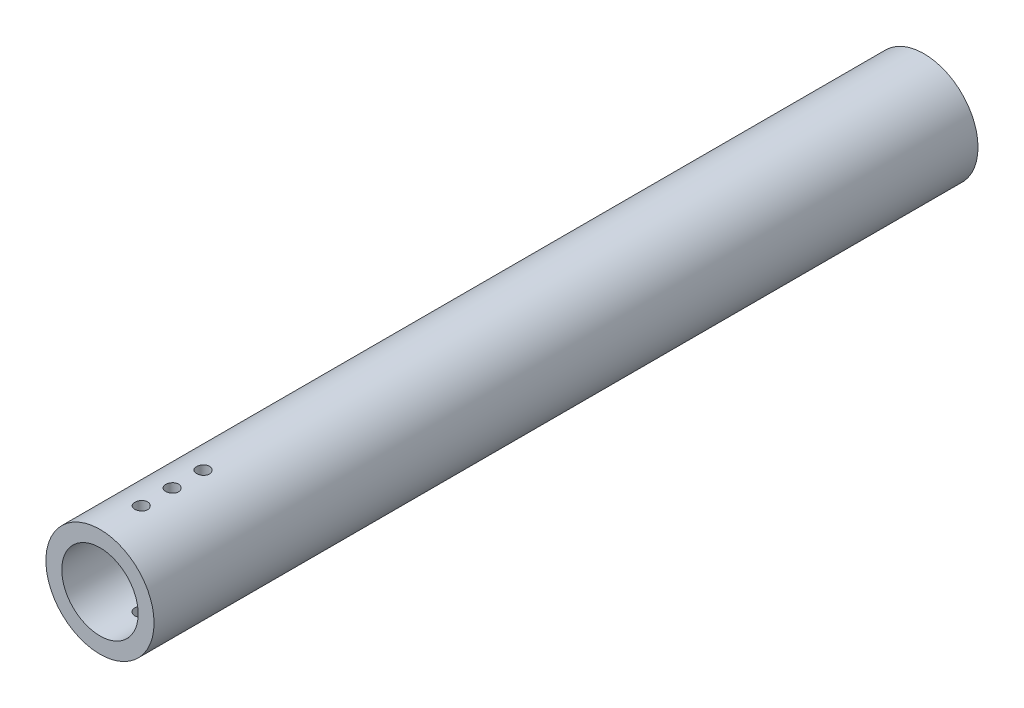
SolidWorks part; units mm, degrees
ref_plane "Front Plane" through (0, 0, 0) normal (0, 0, 1) x (1, 0, 0)
ref_plane "Top Plane" through (0, 0, 0) normal (0, 1, 0) x (1, 0, 0)
ref_plane "Right Plane" through (0, 0, 0) normal (1, 0, 0) x (0, 0, -1)
sketch "Sketch1" plane through (0, 0, 0) normal (0, 0, 1) x (1, 0, 0)
  circle A0 centre (0, 0) radius 13.335
  dimension "Pipe OD" = 26.67
extrude "Extrude-Thin1" add sketch "Sketch1" along normal mid plane 203.2 thin thin type one direction reverse wall 3.9116
sketch "Sketch2" plane through (0, 0, 0) normal (0, 1, 0) x (1, 0, 0)
  line L0 (-13.335, -101.6) -> (13.335, -101.6) construction
  line L1 (0, -91.44) -> (0, 0) construction
  circle A0 centre (0, -91.44) radius 1.5875
  circle A1 centre (0, -83.82) radius 1.5875
  circle A2 centre (0, -76.2) radius 1.5875
  dimension "D1" = 3.175
  dimension "D3" = 3.175
  dimension "D4" = 3.175
  dimension "D2" = 10.16
  dimension "D5" = 7.62
  dimension "D6" = 7.62
extrude "Cut-Extrude1" cut sketch "Sketch2" against normal through all both and the other way through all
